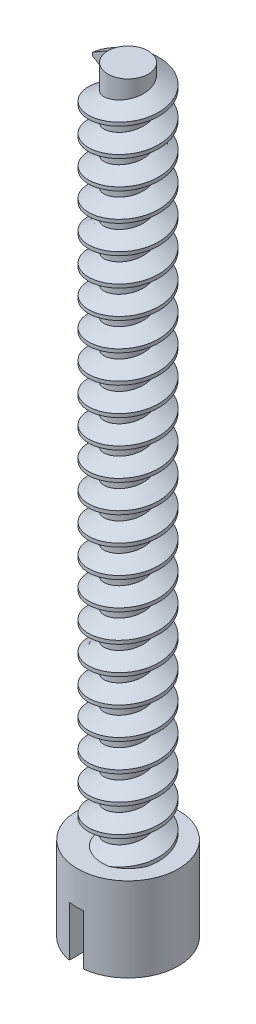
SolidWorks part; units mm, degrees
ref_plane "Front Plane" through (0, 0, 0) normal (0, 0, 1) x (1, 0, 0)
ref_plane "Top Plane" through (0, 0, 0) normal (0, 1, 0) x (1, 0, 0)
ref_plane "Right Plane" through (0, 0, 0) normal (1, 0, 0) x (0, 0, -1)
sketch "Sketch1" plane through (0, 0, 0) normal (0, 1, 0) x (1, 0, 0)
  circle A0 centre (0, 0) radius 3.81
  dimension "D1" = 7.62
extrude "Boss-Extrude1" add sketch "Sketch1" along normal blind 6.35 contours A0
sketch "Sketch2" plane through (0, 6.35, 0) normal (0, 1, 0) x (1, 0, 0)
  circle A0 centre (0, 0) radius 1.524
  dimension "D1" = 3.048
extrude "Boss-Extrude3" add sketch "Sketch2" along normal blind 50.8
thread "Thread1" pitch 2.1167 method extrude profile "Thread Profile1" start angle 0, offset 0, length 0, pitch 2.1167, diameter 3.048
ref_plane "Plane1" through (-1.524, 57.15, 0) normal (0, 0, 1) x (-1, 0, 0)
sketch "Thread Profile1" plane through (-1.524, 57.15, 0) normal (0, 0, 1) x (-1, 0, 0)
  line L0 (0, 0) -> (0, 2.1167) construction
  line L1 (0, 0) -> (1.1457, 0.6615)
  line L2 (1.1457, 0.6615) -> (1.1457, 0.926)
  line L3 (1.1457, 0.926) -> (0, 1.5875)
  line L4 (1.1457, 0.7937) -> (0, 0.7937) construction
  line L11 (0, 0) -> (0, 1.5875)
  point P2 (0, 0)
  dimension "Pitch" = 2.1167
  dimension "Profile_Angle" = 60
  dimension "Profile_Land" = 0.2646
  dimension "Profile_Height" = 1.1457
sketch "Sketch8" plane through (0, 0, 0) normal (0, -1, 0) x (1, 0, 0)
  line L2 (-0.6851, -6.3129) -> (-0.6851, 6.3129)
  line L4 (0.411, -3.7878) -> (0.411, 3.7878)
  line L5 (-0.6851, -6.3129) -> (0.411, 3.7878) construction
  line L6 (-0.6851, 6.3129) -> (0.411, -3.7878) construction
  circle A0 centre (0, 0) radius 3.81 construction
  arc A1 (-0.6851, 6.3129) -> (0.411, 3.7878) centre (-5.8234, 2.5821) cw
  arc A2 (-0.6851, -6.3129) -> (0.411, -3.7878) centre (-5.8234, -2.5821) ccw
  point P0 (0, 0)
extrude "Cut-Extrude2" cut sketch "Sketch8" against normal blind 3.81
